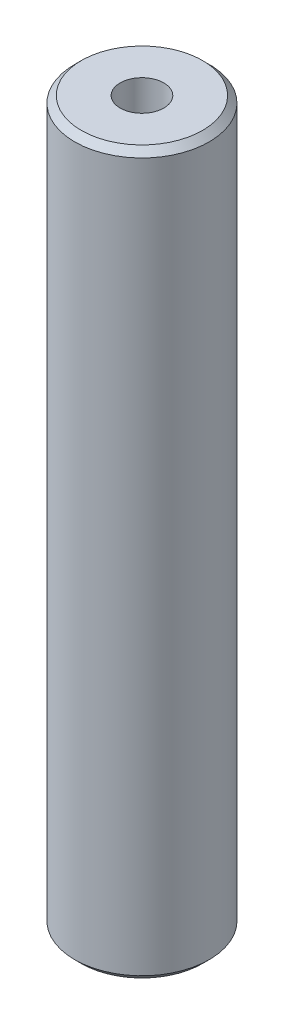
SolidWorks part; units mm, degrees
ref_plane "Front Plane" through (0, 0, 0) normal (0, 0, 1) x (1, 0, 0)
ref_plane "Top Plane" through (0, 0, 0) normal (0, 1, 0) x (1, 0, 0)
ref_plane "Right Plane" through (0, 0, 0) normal (1, 0, 0) x (0, 0, -1)
sketch "Sketch1" plane through (0, 0, 0) normal (0, 1, 0) x (1, 0, 0)
  circle A0 centre (0, 0) radius 45
  dimension "SHAFT_OD" = 90
extrude "Boss-Extrude1" add sketch "Sketch1" along normal blind 483.0268
sketch "Sketch2" plane through (0, 0, 0) normal (0, 1, 0) x (1, 0, 0)
  circle A0 centre (0, 0) radius 14.6123
  dimension "BORE_D" = 29.2245
extrude "Cut-Extrude1" cut sketch "Sketch2" along normal through all
chamfer "Chamfer1" distance 4.4295 angle 45 2 edges at (0, 483.0268, 45) (0, 0, 45)
